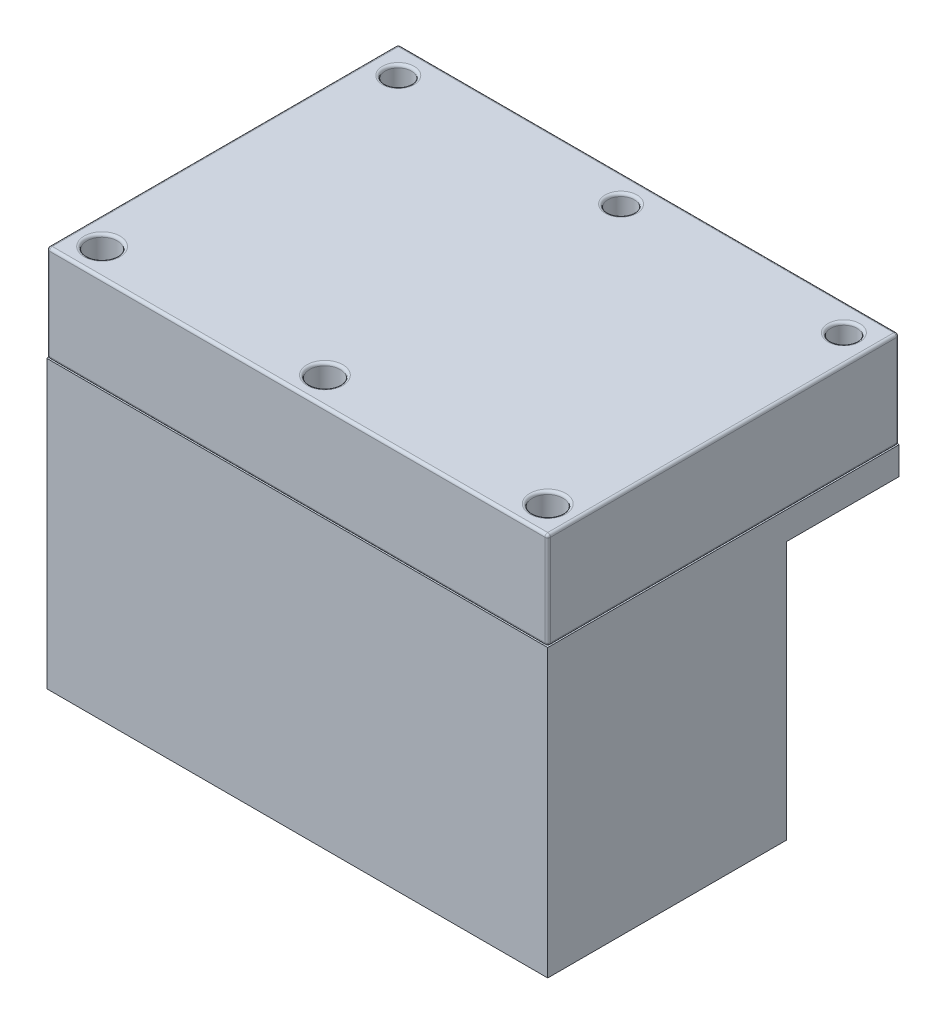
SolidWorks part; units mm, degrees
ref_plane "정면" through (0, 0, 0) normal (0, 0, 1) x (1, 0, 0)
ref_plane "윗면" through (0, 0, 0) normal (0, 1, 0) x (1, 0, 0)
ref_plane "우측면" through (0, 0, 0) normal (1, 0, 0) x (0, 0, -1)
sketch "스케치1" plane through (0, 0, 0) normal (0, 1, 0) x (1, 0, 0)
  line L0 (0, 0) -> (0, 14.3289) construction
  line L1 (-13.1, -7.7) -> (13.1, -7.7)
  line L2 (-13.1, -7.7) -> (-13.1, 7.7)
  line L3 (-13.1, 7.7) -> (13.1, 7.7)
  line L4 (13.1, -7.7) -> (13.1, 7.7)
  line L5 (-13.1, -7.7) -> (13.1, 7.7) construction
  line L6 (-13.1, 7.7) -> (13.1, -7.7) construction
  line L8 (-12.5, 4.75) -> (12.5, 4.75)
  line L9 (-12.5, 4.75) -> (-12.5, 7.3)
  line L10 (-12.5, 7.3) -> (12.5, 7.3)
  line L11 (12.5, 4.75) -> (12.5, 7.3)
  line L12 (-12.5, 4.75) -> (12.5, 7.3) construction
  line L13 (-12.5, 7.3) -> (12.5, 4.75) construction
  circle A0 centre (-10.15, -5.1) radius 1.5
  circle A1 centre (10.15, -5.1) radius 1.5
  point P0 (0, 0)
  point P10 (0, 6.025)
  dimension "D3" = 3
  dimension "D1" = 26.2
  dimension "D2" = 15.4
  dimension "D4" = 20.3
  dimension "D5" = 2.6
  dimension "D6" = 2.55
  dimension "D7" = 25
  dimension "D8" = 0.4
extrude "보스-돌출1" add sketch "스케치1" along normal blind 1.6 contours L1 L4 L3 L2 L11 L8 L9 L10 A0 A1 | L8 L11 L10 L9 region at (0, 0, 0.9582) region at (0, 0, -6.025)
extrude "보스-돌출2" add sketch "스케치1<3>" against normal blind 2.65 contours L8 L11 L10 L9
sketch "스케치1<3>" plane through (0, 0, 0) normal (0, 1, 0) x (1, 0, 0) same geometry as "스케치1"
sketch "스케치2" plane through (0, 1.6, 0) normal (0, 1, 0) x (1, 0, 0)
  line L0 (0, 0) -> (0, -10.3988) construction
  line L1 (0.5, -1.5) -> (-0.5, -1.5)
  line L2 (-0.5, -1.5) -> (-0.5, -5.5)
  line L3 (0.5, -1.5) -> (0.5, -5.5)
  line L4 (-0.5, -5.5) -> (-1.2, -5.5)
  line L5 (0.5, -5.5) -> (1.2, -5.5)
  line L6 (-1.2, -5.5) -> (0, -6.9301)
  line L7 (1.2, -5.5) -> (0, -6.9301)
  line L8 (-5.5, 1.2) -> (-6.9301, 0) [skipped]
  line L9 (-5.5, -1.2) -> (-6.9301, 0) [skipped]
  line L10 (-5.5, -0.5) -> (-5.5, -1.2) [skipped]
  line L11 (-1.5, -0.5) -> (-5.5, -0.5) [skipped]
  line L12 (-1.5, -0.5) -> (-1.5, 0.5) [skipped]
  line L13 (-1.5, 0.5) -> (-5.5, 0.5) [skipped]
  line L14 (-5.5, 0.5) -> (-5.5, 1.2) [skipped]
  line L15 (1.2, 5.5) -> (0, 6.9301) [skipped]
  line L16 (-1.2, 5.5) -> (0, 6.9301) [skipped]
  line L17 (-0.5, 5.5) -> (-1.2, 5.5) [skipped]
  line L18 (-0.5, 1.5) -> (-0.5, 5.5) [skipped]
  line L19 (-0.5, 1.5) -> (0.5, 1.5) [skipped]
  line L20 (0.5, 1.5) -> (0.5, 5.5) [skipped]
  line L21 (0.5, 5.5) -> (1.2, 5.5) [skipped]
  line L22 (5.5, -1.2) -> (6.9301, 0)
  line L23 (5.5, 1.2) -> (6.9301, 0)
  line L24 (5.5, 0.5) -> (5.5, 1.2)
  line L25 (1.5, 0.5) -> (5.5, 0.5)
  line L26 (1.5, 0.5) -> (1.5, -0.5)
  line L27 (1.5, -0.5) -> (5.5, -0.5)
  line L28 (5.5, -0.5) -> (5.5, -1.2)
  text T0 "<b>IMU</b>" font "Century Gothic" height 3.5
  text T1 "<b>X</b>" font "Century Gothic" height in points 8
  text T2 "<b>Y</b>" font "Century Gothic" height in points 8
  point P4 (0, -1.5)
  point P36 (0, 0)
  dimension "D1" = 1
  dimension "D2" = 0.7
  dimension "D3" = 130
  dimension "D4" = 4
  dimension "D5" = 1.5
  dimension "D6" = 4
extrude "보스-돌출3" add sketch "스케치2" along normal blind 1.7
sketch "스케치3" plane through (0, 0, 0) normal (0, -1, 0) x (1, 0, 0)
  line L0 (13.1, 7.7) -> (-13.1, 7.7) construction
  line L1 (-13.1, 7.7) -> (-13.1, -7.7) construction
  line L2 (-13.1, -7.7) -> (13.1, -7.7) construction
  line L3 (13.1, -7.7) -> (13.1, 7.7) construction
  line L4 (-12.5, -4.75) -> (-12.5, -7.3) construction
  line L5 (-12.5, -7.3) -> (12.5, -7.3) construction
  line L6 (12.5, -7.3) -> (12.5, -4.75) construction
  line L7 (12.5, -4.75) -> (-12.5, -4.75) construction
  line L8 (13.1, 7.7) -> (-13.1, 7.7) construction
  line L9 (-13.1, 7.7) -> (-13.1, -7.7) construction
  line L10 (-13.1, -7.7) -> (13.1, -7.7) construction
  line L11 (13.1, -7.7) -> (13.1, 7.7) construction
  line L12 (-12.5, -4.75) -> (-12.5, -7.3) construction
  line L13 (-12.5, -7.3) -> (12.5, -7.3) construction
  line L14 (12.5, -7.3) -> (12.5, -4.75)
  line L15 (12.5, -4.75) -> (-12.5, -4.75) construction
  line L16 (-13.1, 7.7) -> (13.1, 7.7) construction
  line L17 (-18.1, 12.7) -> (18.1, 12.7)
  line L18 (-18.1, 12.7) -> (-18.1, -12.7)
  line L19 (-18.1, -12.7) -> (18.1, -12.7)
  line L20 (18.1, 12.7) -> (18.1, -12.7)
  line L29 (-12.7, -4.55) -> (-12.7, -7.5)
  line L30 (-12.7, -7.5) -> (12.7, -7.5)
  line L31 (12.7, -7.5) -> (12.7, -4.55)
  line L32 (12.7, -4.55) -> (-12.7, -4.55)
  line L33 (-12.7, -4.55) -> (-12.7, -7.5)
  line L34 (-12.7, -7.5) -> (12.7, -7.5)
  line L35 (12.7, -7.5) -> (12.7, -4.55)
  line L36 (12.7, -4.55) -> (-12.7, -4.55)
  circle A0 centre (10.15, 5.1) radius 1.5 construction
  circle A1 centre (-10.15, 5.1) radius 1.5 construction
  circle A2 centre (10.15, 5.1) radius 1.5 construction
  circle A3 centre (-10.15, 5.1) radius 1.5 construction
  circle A4 centre (-10.15, 5.1) radius 1.45
  circle A5 centre (10.15, 5.1) radius 1.45
  circle M20 centre (10.15, 5.1) radius 1.5
  circle M21 centre (-10.15, 5.1) radius 1.5
  line M22 (13.1, 7.7) -> (-13.1, 7.7)
  line M23 (-13.1, 7.7) -> (-13.1, -7.7)
  line M24 (-13.1, -7.7) -> (13.1, -7.7)
  line M25 (13.1, -7.7) -> (13.1, 7.7)
  dimension "D6" = 2.9
  dimension "D1" = 5
  dimension "D2" = 5
  dimension "D3" = 5
  dimension "D4" = 5
  dimension "D5" = 0.2
extrude "보스-돌출4" add sketch "스케치3" along normal blind 2 separate body contours L20 L17 L18 L19 M22 M25 M24 M23 | L36 L35 L34 L33 M25 M22 M23 M24 M21 M20 region at (0, 0, 12.2578) region at (0, 0, 1.2065)
sketch "스케치4" plane through (0, 0, 0) normal (0, 1, 0) x (1, 0, 0)
  line L0 (14.1, 8.7) -> (-14.1, 8.7)
  line L1 (-14.1, 8.7) -> (-14.1, -8.7)
  line L2 (-14.1, -8.7) -> (14.1, -8.7)
  line L3 (14.1, -8.7) -> (14.1, 8.7)
  line L4 (18.1, -12.7) -> (18.1, 12.7)
  line L5 (18.1, 12.7) -> (-18.1, 12.7)
  line L6 (-18.1, 12.7) -> (-18.1, -12.7)
  line L7 (-18.1, -12.7) -> (18.1, -12.7)
  line L8 (18.1, -12.7) -> (18.1, 12.7)
  line L9 (18.1, 12.7) -> (-18.1, 12.7)
  line L10 (-18.1, 12.7) -> (-18.1, -12.7)
  line L11 (-18.1, -12.7) -> (18.1, -12.7)
  line L12 (0, 0) -> (0, -14.647) construction
  circle A2 centre (-16.1, 10.7) radius 0.95
  circle A3 centre (16.1, 10.7) radius 0.95
  circle A4 centre (-16.1, -10.7) radius 1.1
  circle A5 centre (16.1, -10.7) radius 1.1
  circle A6 centre (0, -10.7) radius 1.1
  circle A7 centre (0, 10.7) radius 0.95
  line M16 (18.1, -12.7) -> (18.1, 12.7)
  line M17 (18.1, 12.7) -> (-18.1, 12.7)
  line M18 (-18.1, 12.7) -> (-18.1, -12.7)
  line M19 (-18.1, -12.7) -> (18.1, -12.7)
  dimension "D3" = 2
  dimension "D5" = 2
  dimension "D7" = 1.9
  dimension "D8" = 2.2
  dimension "D4" = 2
  dimension "D6" = 2
  dimension "D1" = 0
  dimension "D2" = 4
extrude "보스-돌출5" add sketch "스케치4" along normal blind 5 separate body contours L3 L2 A6 L11 L1 L0 A7 A3 A2 A4 A5 M16 M17 M18 M19 region at (0, 0, 12.2578)
sketch "스케치5" plane through (0, 5, 0) normal (0, 1, 0) x (1, 0, 0)
  line L4 (-18.1, 12.7) -> (-18.1, -12.7)
  line L5 (-18.1, -12.7) -> (18.1, -12.7)
  line L6 (18.1, -12.7) -> (18.1, 12.7)
  line L7 (18.1, 12.7) -> (-18.1, 12.7)
  line L8 (-18.1, 12.7) -> (-18.1, -12.7)
  line L9 (-18.1, -12.7) -> (18.1, -12.7)
  line L10 (18.1, -12.7) -> (18.1, 12.7)
  line L11 (18.1, 12.7) -> (-18.1, 12.7)
  circle A0 centre (-16.1, -10.7) radius 1.1 construction
  circle A1 centre (0, -10.7) radius 1.1 construction
  circle A2 centre (16.1, -10.7) radius 1.1 construction
  circle A3 centre (16.1, 10.7) radius 0.95 construction
  circle A4 centre (0, 10.7) radius 0.95 construction
  circle A5 centre (-16.1, 10.7) radius 0.95 construction
  circle A6 centre (-16.1, -10.7) radius 1.1
  circle A7 centre (0, -10.7) radius 1.1
  circle A8 centre (16.1, -10.7) radius 1.1
  circle A9 centre (16.1, 10.7) radius 0.95
  circle A10 centre (0, 10.7) radius 0.95
  circle A11 centre (-16.1, 10.7) radius 0.95
  dimension "D1" = 0
extrude "보스-돌출6" add sketch "스케치5" along normal blind 2
sketch "스케치6" plane through (0, -2, 0) normal (0, -1, 0) x (1, 0, 0)
  line L0 (-18.1, -4.55) -> (18.1, -4.55)
  line L1 (12.7, -4.55) -> (-12.7, -4.55) construction
  line L4 (18.1, -12.7) -> (18.1, 12.7)
  line L5 (18.1, 12.7) -> (-18.1, 12.7)
  line L6 (-18.1, 12.7) -> (-18.1, -12.7)
  line L7 (-18.1, -12.7) -> (18.1, -12.7)
  line L8 (18.1, -12.7) -> (18.1, 12.7)
  line L9 (18.1, 12.7) -> (-18.1, 12.7)
  line L10 (-18.1, 12.7) -> (-18.1, -12.7)
  line L11 (-18.1, -12.7) -> (18.1, -12.7)
  circle A0 centre (10.15, 5.1) radius 1.5 construction
  circle A1 centre (-10.15, 5.1) radius 1.5 construction
  circle A2 centre (10.15, 5.1) radius 1.5
  circle A3 centre (-10.15, 5.1) radius 1.5
  line M6 (18.1, -12.7) -> (18.1, 12.7)
  line M7 (18.1, 12.7) -> (-18.1, 12.7)
  line M8 (-18.1, 12.7) -> (-18.1, -12.7)
  line M10 (-12.7, -4.55) -> (12.7, -4.55)
  circle M14 centre (-10.15, 5.1) radius 1.5
  circle M15 centre (10.15, 5.1) radius 1.5
  dimension "D1" = 0
extrude "보스-돌출8" add sketch "스케치6" along normal blind 18.68 contours L0 M8 M10 M6 M7 M14 M15 region at (0, -2, 4.0513)
fillet "필렛1" radius 0.2 36 edges at (-14.1, 2.5, 8.7) (-14.1, 2.5, -8.7) (0, 0, 8.7) (-14.1, 0, 0) (0, 0, -8.7) (-18.1, 0, 0) (-18.1, 7, 0) (14.1, 2.5, -8.7) (14.1, 2.5, 8.7) (14.1, 0, 0) (0, 5, -8.7) (-14.1, 5, 0) (0, 5, 8.7) (14.1, 5, 0) (0, 7, -12.7) (-18.1, 3.5, -12.7) (0, 0, -12.7) (18.1, 7, 0) (18.1, 3.5, -12.7) (18.1, 0, 0) (-18.1, 3.5, 12.7) (0, 7, 12.7) (18.1, 3.5, 12.7) (0, 0, 12.7) (16.1, 0, 11.8) (-16.1, 0, 11.8) (-16.1, 0, -9.75) (16.1, 0, -9.75) (0, 0, -9.75) (0, 0, 11.8) (-16.1, 7, -9.75) (16.1, 7, -9.75) (0, 7, 11.8) (-16.1, 7, 11.8) (16.1, 7, 11.8) (0, 7, -9.75)
